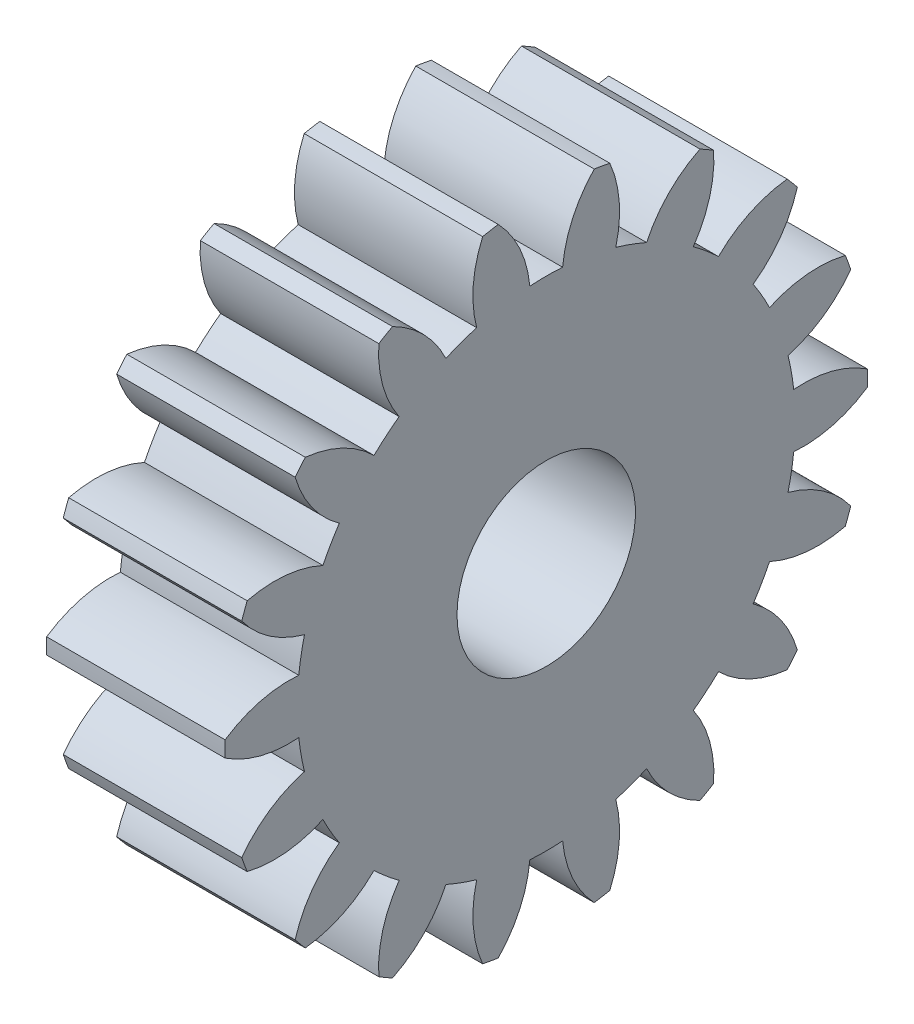
SolidWorks part; units mm, degrees
ref_plane "Plane1" through (0, 0, 0) normal (0, 0, 1) x (1, 0, 0)
ref_plane "Plane2" through (0, 0, 0) normal (0, 1, 0) x (1, 0, 0)
ref_plane "Plane3" through (0, 0, 0) normal (1, 0, 0) x (0, 0, -1)
sketch "HoldingSke" plane through (0, 0, 0) normal (0, 1, 0) x (1, 0, 0)
  line L0 (0, 0) -> (1.0567, -0.3434)
  line L1 (-15, 0) -> (100, 0) construction
  line L2 (0, 0) -> (-2.1039, 2.3779)
  line L3 (0, 0) -> (-11.863, 4.5341)
  line L4 (0, 0) -> (8.2133, 2.6687)
  line L5 (0, 0) -> (-46.8476, -17.4728)
  line L6 (0, 0) -> (-4.1448, -2.7965)
  line L7 (-2.1039, 2.3779) -> (8.6586, 51.2059)
  line L8 (-76.2, 54.61) -> (-75.3, 54.61)
  line L9 (-71.009, 38.7566) -> (-53.1078, 45.2721)
  line L10 (-76.2, 71.12) -> (104.1128, 71.12)
  line L11 (0, 0) -> (-5, 0)
  line L12 (-76.2, 101.6) -> (-76.166, 101.6)
  line L13 (24.9733, 27.94) -> (52.9518, 28.4284)
  line L14 (24.9733, 27.94) -> (24.9743, 27.94)
  line L15 (24.9733, 27.94) -> (100.4006, 29.5858)
  line L16 (-63.627, -0.9) -> (-12.827, -0.9)
  circle A0 centre (0, 0) radius 2.5
  circle A1 centre (0, 0) radius 6.974
  circle A2 centre (0, 0) radius 37.5
  circle A3 centre (0, 0) radius 2.5
  dimension "Num_teeth" = 18
  dimension "Pitch_radius" = 180.3128
  dimension "Width" = 5
  dimension "Thickness" = 5
sketch "BasProSke" plane through (0, 0, 0) normal (0, 1, 0) x (1, 0, 0)
  line L0 (-10, 0) -> (60, 0) construction
  line L1 (0, 0) -> (0, 9)
  line L2 (0, 0) -> (5, 0)
  line L3 (5, 0) -> (5, 9)
  line L4 (5, 9) -> (0, 9)
  dimension "Thickness" = 5
  dimension "Diameter" = 18
revolve "Base-Revolve" add sketch "BasProSke" angle 360 about L0
sketch "TooCutSke" plane through (0, 0, 0) normal (1, 0, 0) x (0, 0, -1)
  line L1 (0, 0) -> (0, 107) construction
  line L2 (0, 0) -> (-0.7654, 8.0638) construction
  line L3 (0, 0) -> (-2.8041, 15.903) construction
  line L4 (-0.7654, 8.0638) -> (-1.4021, 7.9515) construction
  arc A0 (0.4593, 6.9589) -> (-0.4593, 6.9589) centre (0, 0) ccw
  arc A1 (1.3655, 8.9215) -> (-1.3655, 8.9215) centre (0, 0) ccw
  circle A2 centre (0, 0) radius 8.1 construction
  circle A3 centre (0, 0) radius 7.6115 construction
  arc A4 (-0.4593, 6.9589) -> (-1.3655, 8.9215) centre (-3.6854, 6.6598) ccw
  arc A5 (1.3655, 8.9215) -> (0.4593, 6.9589) centre (3.6854, 6.6598) ccw
extrude "ToothCut" cut sketch "TooCutSke" along normal through all
fillet "Breaks" [suppressed] radius 0.018 tangent propagation no
fillet "RootFillets" [suppressed] radius 0.226
pattern_circular "TeethCuts" count 18 every 20 about axis through (-10, 0, 0) along (1, 0, 0) of "ToothCut", "RootFillets", "Breaks"
sketch "HubNeaOneSke" plane through (0, 0, 0) normal (-1, 0, 0) x (0, 0, 1)
  circle A0 centre (0, 0) radius 6.974
  dimension "Diameter" = 13.948
extrude "HubNearOne" [suppressed] add sketch "HubNeaOneSke" along normal blind 45.0001
sketch "HubNeaBotSke" plane through (0, 0, 0) normal (-1, 0, 0) x (0, 0, 1)
  circle A0 centre (0, 0) radius 6.974
  dimension "Diameter" = 13.948
extrude "HubNearBoth" [suppressed] add sketch "HubNeaBotSke" along normal blind 22.5
ref_plane "FarPln" through (5, 0, 0) normal (1, 0, 0) x (0, 0, -1)
sketch "HubFarSke" plane through (5, 0, 0) normal (1, 0, 0) x (0, 0, -1)
  circle A0 centre (0, 0) radius 6.974
  dimension "Diameter" = 13.948
extrude "HubFar" [suppressed] add sketch "HubFarSke" along normal blind 22.5
sketch "BorSke" plane through (0, 0, 0) normal (1, 0, 0) x (0, 0, -1)
  circle A0 centre (0, 0) radius 2.5
  dimension "Diameter" = 5
extrude "Bore" cut sketch "BorSke" along normal mid plane 100.0001
sketch "KeySke" plane through (0, 0, 0) normal (1, 0, 0) x (0, 0, -1)
  line L0 (-1, 0) -> (-1, 3.4)
  line L1 (-1, 3.4) -> (1, 3.4)
  line L2 (1, 3.4) -> (1, 0)
  line L3 (0, 0) -> (0, 34) construction
  line L4 (-1, 0) -> (1, 0)
  dimension "Width" = 2
extrude "Keyway" [suppressed] cut sketch "KeySke" along normal mid plane 100.0001
pattern_circular "Keyway2" [suppressed] count 2 every 90 about axis through (-10, 0, 0) along (1, 0, 0) reverse direction yes
equation "' \"Module@HoldingSke\" = 6.35"
equation "' \"Num_teeth@HoldingSke\" = 12"
equation "' \"Ap@HoldingSke\" =  20"
equation "' \"Ap@HoldingSke\" = 20"
equation "' \"Width@HoldingSke\" = 0.5 * 25.4"
equation "' \"Hub_dia@HoldingSke\"= 1 * 25.4"
equation "' \"Hub_dia@HoldingSke\" = 1 * 25.4"
equation "' \"Overall_len@HoldingSke\" = 1.0 * 25.4"
equation "' \"Bore@HoldingSke\" = 0.75 * 25.4"
equation "' \"T_dim@HoldingSke\" = 0.1 * 25.4"
equation "' \"Width@KeySke\" = 0.25 * 25.4"
equation "' \"Show_teeth@HoldingSke\" = 13"
equation "' \"Backlash@HoldingSke\" = 0.009 * 25.4"
equation "' \"Addendum_fac@HoldingSke\" = 1.0"
equation "' \"Dedendum_fac@HoldingSke\" = 1.25"
equation "' \"Dedendum_add@HoldingSke\" = 0.00005 * 25.4"
equation "' \"Clearance_fac@HoldingSke\" = 0.25"
equation "\"Pitch@HoldingSke\" = 1 / \"Module@HoldingSke\""
equation "\"Overcut_dia@TooCutSke\" = (\"Num_teeth@HoldingSke\" + 2 * \"Addendum_fac@HoldingSke\") / \"Pitch@HoldingSke\" + 0.002 * 25.4"
equation "\"Pitch_dia@TooCutSke\" = \"Num_teeth@HoldingSke\" / \"Pitch@HoldingSke\""
equation "\"Base_dia@TooCutSke\" = \"Num_teeth@HoldingSke\" / \"Pitch@HoldingSke\" * cos((\"Ap@HoldingSke\"  * 3.14159265 / 180))"
equation "\"Root_dia@TooCutSke\" = (\"Num_teeth@HoldingSke\" + 2) / \"Pitch@HoldingSke\" - 2 * (\"Addendum_fac@HoldingSke\" + \"Dedendum_fac@HoldingSke\") / \"Pitch@HoldingSke\" - \"Dedendum_add@HoldingSke\" * 2"
equation "\"Half_ang@TooCutSke\" = 180 / \"Num_teeth@HoldingSke\""
equation "\"Half_CT@TooCutSke\" = \"Num_teeth@HoldingSke\" / \"Pitch@HoldingSke\" * sin((3.14159265 / 2 / \"Num_teeth@HoldingSke\")) / 2 - 7 * \"Backlash@HoldingSke\" / 4"
equation "\"Flank_rad@TooCutSke\" = \"Num_teeth@HoldingSke\" / \"Pitch@HoldingSke\" / 5"
equation "\"Radius@RootFillets\" = \"Clearance_fac@HoldingSke\" / \"Pitch@HoldingSke\" + \"Dedendum_add@HoldingSke\""
equation "\"Break_rad@Breaks\" = 0.02 / \"Pitch@HoldingSke\""
equation "\"Thickness@HoldingSke\" = \"Width@HoldingSke\""
equation "\"OAL@HoldingSke\" = \"Thickness@HoldingSke\""
equation "\"MHD@HoldingSke\" = (\"Num_teeth@HoldingSke\" + 2) / \"Pitch@HoldingSke\" - 2 * (\"Addendum_fac@HoldingSke\" + \"Dedendum_fac@HoldingSke\")  / \"Pitch@HoldingSke\" - \"Dedendum_add@HoldingSke\" * 2"
equation "\"MBD@HoldingSke\" = (\"Num_teeth@HoldingSke\" + 2) / \"Pitch@HoldingSke\" - 2 * (\"Addendum_fac@HoldingSke\" + \"Dedendum_fac@HoldingSke\")  / \"Pitch@HoldingSke\" - \"Dedendum_add@HoldingSke\" * 2 - 0.002 * 25.4"
equation "\"MHD@HoldingSke\" = ((sgn( \"MHD@HoldingSke\" - \"Hub_dia@HoldingSke\" )-1)*( \"MHD@HoldingSke\" - \"Hub_dia@HoldingSke\" ))/-2+ \"Hub_dia@HoldingSke\""
equation "\"MBD@HoldingSke\" = ((sgn( \"MBD@HoldingSke\" - \"Bore@HoldingSke\" )-1)*( \"MBD@HoldingSke\" - \"Bore@HoldingSke\" ))/-2+ \"Bore@HoldingSke\""
equation "\"OAL@HoldingSke\" = ((sgn( \"OAL@HoldingSke\" - \"Overall_len@HoldingSke\" )+1)*( \"OAL@HoldingSke\" - \"Overall_len@HoldingSke\" ))/2 + \"Overall_len@HoldingSke\" + 0.000002 * 25.4"
equation "\"Num_teeth@TeethCuts\" = int( \"Show_teeth@HoldingSke\" ) + 1"
equation "\"Num_teeth@TeethCuts\" = ((sgn( \"Num_teeth@TeethCuts\" - \"Num_teeth@HoldingSke\" )-1)*( \"Num_teeth@TeethCuts\" - \"Num_teeth@HoldingSke\" ))/-2+ \"Num_teeth@HoldingSke\""
equation "\"Num_teeth@TeethCuts\" = ((sgn( \"Num_teeth@TeethCuts\" - 2.0)+1)*( \"Num_teeth@TeethCuts\" - 2.0))/2 +2.0"
equation "\"Angle@TeethCuts\" = 360.0 / \"Num_teeth@HoldingSke\""
equation "\"Diameter@BasProSke\" = (\"Num_teeth@HoldingSke\" + 2 * \"Addendum_fac@HoldingSke\") / \"Pitch@HoldingSke\""
equation "\"Thickness@BasProSke\"  = \"Thickness@HoldingSke\""
equation "' \"Fillet_rad@BasProSke\" =  \"Thickness@HoldingSke\" * 0.05"
equation "' \"Fillet_rad@BasProSke\" = \"Thickness@HoldingSke\" * 0.05"
equation "\"MHD@HoldingSke\" = ((sgn( \"MHD@HoldingSke\" - \"Root_dia@TooCutSke\" )-1)*( \"MHD@HoldingSke\" - \"Root_dia@TooCutSke\" ))/-2+ \"Root_dia@TooCutSke\""
equation "\"Diameter@HubNeaOneSke\" = \"MHD@HoldingSke\""
equation "\"Length@HubNearOne\" = \"OAL@HoldingSke\" - \"Thickness@BasProSke\""
equation "\"Diameter@HubNeaBotSke\" = \"MHD@HoldingSke\""
equation "\"Length@HubNearBoth\" = ( \"OAL@HoldingSke\" - \"Thickness@BasProSke\" ) / 2.0"
equation "\"Thickness@FarPln\" = \"Thickness@BasProSke\""
equation "\"Diameter@HubFarSke\" = \"MHD@HoldingSke\""
equation "\"Length@HubFar\" = ( \"OAL@HoldingSke\" - \"Thickness@BasProSke\" ) / 2.0"
equation "\"Diameter@BorSke\" = \"MBD@HoldingSke\""
equation "\"D1@Bore\" = \"OAL@HoldingSke\" * 2.0"
equation "\"D1@Keyway\" = \"OAL@HoldingSke\" * 2.0"
equation "\"Offset@KeySke\" = \"T_dim@HoldingSke\" + \"MBD@HoldingSke\" / 2.0"
